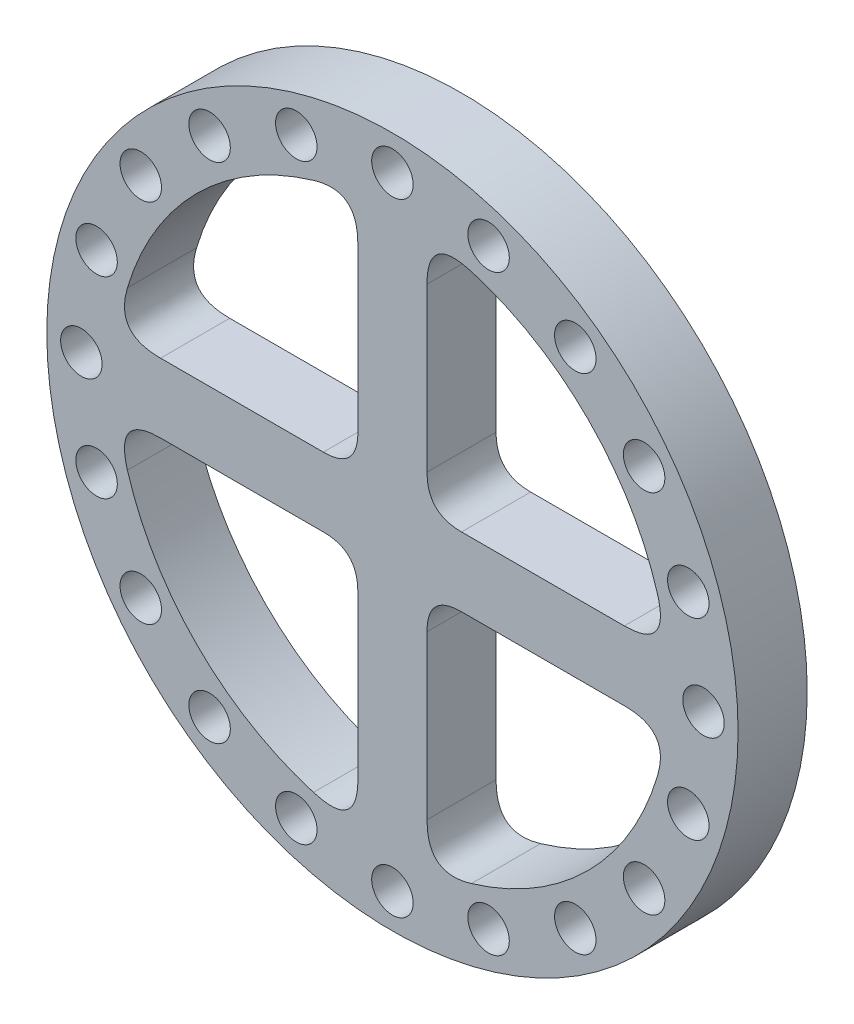
SolidWorks part; units mm, degrees
ref_plane "Plano frontal" through (0, 0, 0) normal (0, 0, 1) x (1, 0, 0)
ref_plane "Plano superior" through (0, 0, 0) normal (0, 1, 0) x (1, 0, 0)
ref_plane "Plano direito" through (0, 0, 0) normal (1, 0, 0) x (0, 0, -1)
sketch "Esboço1" plane through (0, 0, 0) normal (0, 0, 1) x (1, 0, 0)
  circle A0 centre (0, 0) radius 40
  circle A1 centre (0, 0) radius 50
  dimension "D1" = 100
  dimension "D2" = 80
extrude "Ressalto-extrusão1" add sketch "Esboço1" along normal blind 10 contours A0 | A1
sketch "Esboço2" plane through (0, 0, 10) normal (0, 0, 1) x (1, 0, 0)
  circle A0 centre (0, 0) radius 45 construction
  circle A1 centre (45, 0) radius 3
  circle A2 centre (42.7975, -13.9058) radius 3
  circle A3 centre (36.4058, -26.4503) radius 3
  circle A4 centre (26.4503, -36.4058) radius 3
  circle A5 centre (13.9058, -42.7975) radius 3
  circle A6 centre (0, -45) radius 3
  circle A7 centre (-13.9058, -42.7975) radius 3
  circle A8 centre (-26.4503, -36.4058) radius 3
  circle A9 centre (-36.4058, -26.4503) radius 3
  circle A10 centre (-42.7975, -13.9058) radius 3
  circle A11 centre (-45, 0) radius 3
  circle A12 centre (-42.7975, 13.9058) radius 3
  circle A13 centre (-36.4058, 26.4503) radius 3
  circle A14 centre (-26.4503, 36.4058) radius 3
  circle A15 centre (-13.9058, 42.7975) radius 3
  circle A16 centre (0, 45) radius 3
  circle A17 centre (13.9058, 42.7975) radius 3
  circle A18 centre (26.4503, 36.4058) radius 3
  circle A19 centre (36.4058, 26.4503) radius 3
  circle A20 centre (42.7975, 13.9058) radius 3
  point P46 (0, 0)
  dimension "D1" = 90
  dimension "D2" = 6
  dimension "D3" = 20
extrude "Corte-extrusão1" cut sketch "Esboço2" against normal blind 10
sketch "Esboço3" plane through (0, 0, 10) normal (0, 0, 1) x (1, 0, 0)
  line L1 (0, 40) -> (0, 39.6863) construction
  line L2 (-39.6863, -5) -> (-5, -5)
  line L3 (-39.6863, 5) -> (-5, 5)
  line L5 (-5, 39.6863) -> (-5, 5)
  line L6 (5, 39.6863) -> (5, 5)
  line L10 (-5, 40) -> (-5, -60) construction
  line L11 (0, 40) -> (0, -60) construction
  line L12 (5, 40) -> (5, -60) construction
  line L13 (5, 5) -> (39.6863, 5)
  line L14 (-5, -5) -> (-5, -39.6863)
  line L15 (5, -5) -> (39.6863, -5)
  line L16 (5, -5) -> (5, -39.6863)
  arc A1 (39.6863, -5) -> (39.6863, 5) centre (0, 0) ccw
  arc A2 (-5, -39.6863) -> (5, -39.6863) centre (0, 0) ccw
  arc A3 (-39.6863, 5) -> (-39.6863, -5) centre (0, 0) ccw
  arc A4 (5, 39.6863) -> (-5, 39.6863) centre (0, 0) ccw
  point P0 (0, 0)
  point P4 (0, 0)
  point P10 (0, 0)
  point P27 (0, 0)
  point P28 (0, 0)
  dimension "D3" = 5
  dimension "D4" = 5
extrude "Ressalto-extrusão2" add sketch "Esboço3" against normal blind 10
fillet "Filete3" radius 5 12 edges at (-39.6863, -5, 5) (39.6863, 5, 5) (5, 5, 5) (5, 39.6863, 5) (5, -5, 5) (5, -39.6863, 5) (-5, -39.6863, 5) (39.6863, -5, 5) (-5, 39.6863, 5) (-5, -5, 5) (-39.6863, 5, 5) (-5, 5, 5) conic rho 0.5
